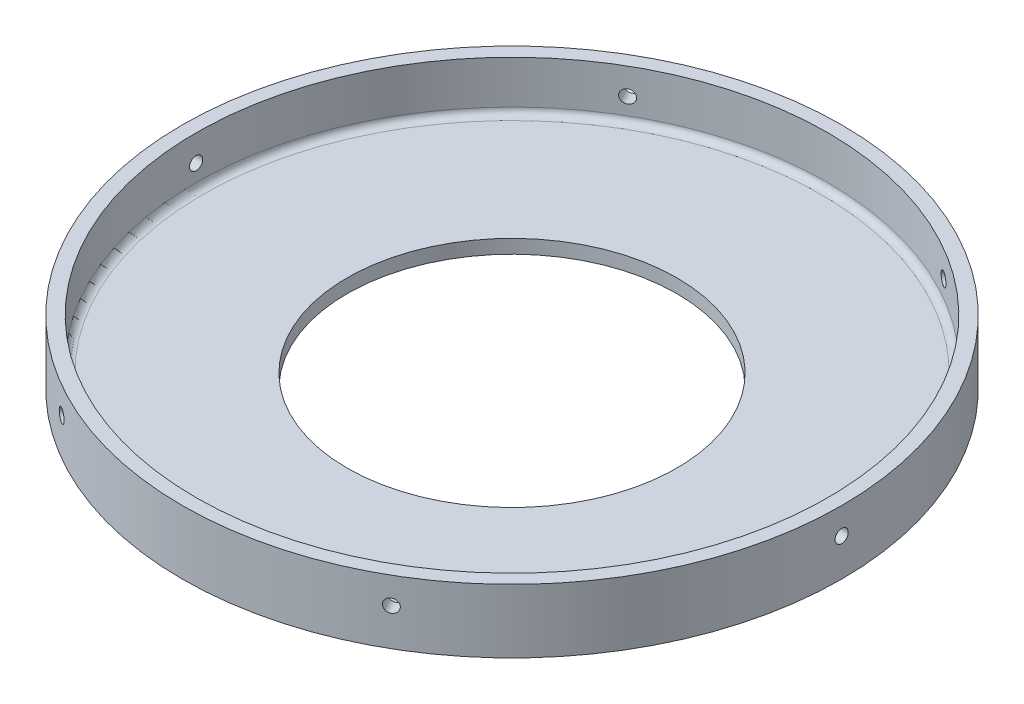
SolidWorks part; units mm, degrees
material "6061-T6 (SS)"
ref_plane "Front Plane" through (0, 0, 0) normal (0, 0, 1) x (1, 0, 0)
ref_plane "Top Plane" through (0, 0, 0) normal (0, 1, 0) x (1, 0, 0)
ref_plane "Right Plane" through (0, 0, 0) normal (1, 0, 0) x (0, 0, -1)
sketch "Sketch1" plane through (0, 0, 0) normal (0, 1, 0) x (1, 0, 0)
  circle A0 centre (0, 0) radius 76.2
extrude "Boss-Extrude1" add sketch "Sketch1" along normal blind 16.256
shell "Shell1" thickness 3.175 removed face at (0, 16.256, 76.2)
fillet "Fillet1" radius 1.5875 1 edges at (0, 3.175, 73.025)
sketch "Sketch2" plane through (0, 0, 0) normal (0, -1, 0) x (1, 0, 0)
  circle A0 centre (0, 0) radius 38.1
  dimension "D1" = 76.2
extrude "Cut-Extrude1" cut sketch "Sketch2" against normal blind 16.256
sketch "Sketch3" plane through (0, 0, 0) normal (1, 0, 0) x (0, 0, -1)
  line L0 (0, 0) -> (0, 8.636) construction
  circle A0 centre (0, 8.636) radius 1.524
  dimension "D2" = 3.048
  dimension "D1" = 8.636
extrude "Cut-Extrude2" cut sketch "Sketch3" against normal blind 76.2
pattern_circular "CirPattern1" count 6 over 360 about axis through (0, 16.256, 0) along (0, -1, 0) of "Cut-Extrude2"
sketch "Sketch5" plane through (0, 16.256, 0) normal (0, 1, 0) x (1, 0, 0)
  circle A0 centre (0, 0) radius 76.2
extrude "Cut-Extrude4" cut sketch "Sketch5" against normal blind 1.524
